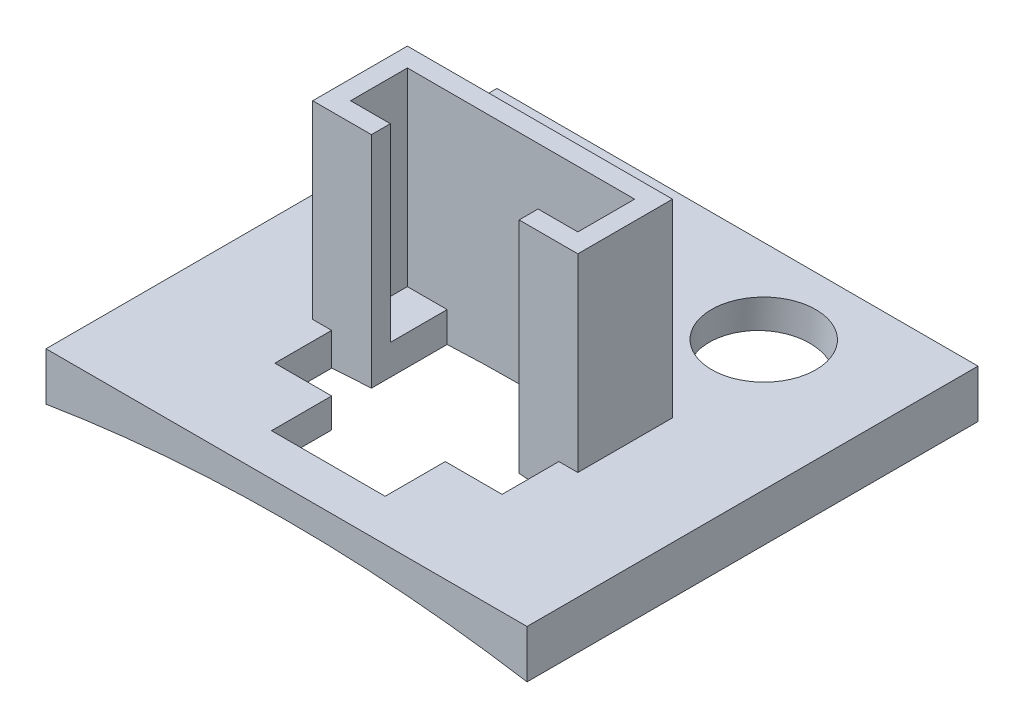
SolidWorks part; units mm, degrees
ref_plane "Front Plane" through (0, 0, 0) normal (0, 0, 1) x (1, 0, 0)
ref_plane "Top Plane" through (0, 0, 0) normal (0, 1, 0) x (1, 0, 0)
ref_plane "Right Plane" through (0, 0, 0) normal (1, 0, 0) x (0, 0, -1)
sketch "Sketch1" plane through (0, 0, 0) normal (0, 1, 0) x (1, 0, 0)
  line L0 (6, -10.985) -> (7, -10.985)
  line L1 (-12.7, 4.445) -> (12.7, 4.445)
  line L2 (-12.7, 4.445) -> (-12.7, -19.3675)
  line L3 (-12.7, -19.3675) -> (12.7, -19.3675)
  line L4 (12.7, 4.445) -> (12.7, -19.3675)
  line L5 (-6, -6.985) -> (6, -6.985)
  line L6 (-6, -6.985) -> (-6, -13.985)
  line L7 (-6, -13.985) -> (6, -13.985)
  line L8 (6, -6.985) -> (6, -13.985)
  line L9 (7, -10.985) -> (7, -5.985)
  line L10 (7, -5.985) -> (-7, -5.985)
  line L11 (-7, -5.985) -> (-7, -10.985)
  line L12 (-7, -10.985) -> (-6, -10.985)
  line L13 (6, -10.985) -> (3.9, -10.985)
  line L14 (3.9, -10.985) -> (3.9, -9.985)
  line L15 (3.9, -9.985) -> (6, -9.985)
  line L16 (-6, -10.985) -> (-3.9, -10.985)
  line L17 (-3.9, -10.985) -> (-3.9, -9.985)
  line L18 (-3.9, -9.985) -> (-6, -9.985)
  line L19 (-3.9, -9.985) -> (-3.9, -6.985)
  line L20 (3.9, -9.985) -> (3.9, -6.985)
  line L21 (0, -7.3881) -> (0, 0) construction
  line L22 (-3, -13.985) -> (-3, -17.16)
  line L23 (-3, -17.16) -> (3, -17.16)
  line L24 (3, -17.16) -> (3, -13.985)
  point P23 (0, -19.3675)
  point P24 (0, -17.16)
  point P27 (0, -6.985)
  dimension "D1" = 12
  dimension "D2" = 7
  dimension "D3" = 1
  dimension "D4" = 1
  dimension "D5" = 7.8
  dimension "D6" = 3
  dimension "D7" = 1
  dimension "D8" = 6.985
  dimension "D9" = 23.8125
  dimension "D10" = 25.4
  dimension "D11" = 4.445
  dimension "D12" = 3.175
  dimension "D13" = 6
sketch "Sketch2" plane through (0, 0, 0) normal (0, 0, 1) x (1, 0, 0)
  line L0 (0, 0) -> (0, -76.859) construction
  circle A0 centre (0, -76.859) radius 78.359
  dimension "D1" = 156.718
  dimension "D2" = 76.859
ref_axis "Axis1" through (0, -76.859, 0) along (0, 0, 1)
ref_plane "Plane1" through (-5.5819, -76.4515, 0) normal (0.0728, 0.9973, 0) x (0, 0, 1)
sketch "Sketch3" plane through (-5.5819, -76.4515, 0) normal (0.0728, 0.9973, 0) x (0, 0, 1)
  line L0 (0, -72.7623) -> (0, 83.9557) construction
  circle A0 centre (0, 5.5967) radius 2.75
  dimension "D1" = 5.5
extrude "Boss-Extrude1" add sketch "Sketch1" along normal blind 3 contours L3 L21 L7 L6 L12 L11 L10 L1 L2 | L21 L3 L4 L1 L10 L9 L0 L8 L7 | L5 L21 L10 L11 L12 L6 | L21 L5 L8 L0 L9 L10 | L20 L15 L8 L5 | L18 L19 L5 L6 | L15 L14 L13 L8 | L17 L18 L6 L16 region at (6.086, 0, 10.485) region at (4.95, 0, 10.485) region at (4.95, 0, 8.485) region at (-0.086, 0, 6.485) region at (-4.95, 0, 8.485) region at (-4.95, 0, 10.485) region at (0, 0, -4.0968)
extrude "Cut-Extrude1" cut sketch "Sketch3" along normal through all contours A0
mirror "Mirror1" about plane through (0, 0, 0) normal (1, 0, 0) of "Cut-Extrude1"
extrude "Boss-Extrude2" add sketch "Sketch1<8>" along normal blind 10 from surface contours L5 L21 L10 L11 L12 L6 | L17 L18 L6 L16 | L15 L14 L13 L8 | L21 L5 L8 L0 L9 L10 region at (6.086, 0, 10.485) region at (4.95, 0, 10.485) region at (-0.086, 0, 6.485) region at (-4.95, 0, 10.485) starting at face at (-3.0733, 3, 0)
sketch "Sketch1<8>" plane through (0, 0, 0) normal (0, 1, 0) x (1, 0, 0) same geometry as "Sketch1"
extrude "Cut-Extrude2" cut sketch "Sketch2" against normal through all both and the other way through all
equation "\"D2@Sketch2\"=(6.17/2)*1in - 1.5mm"
